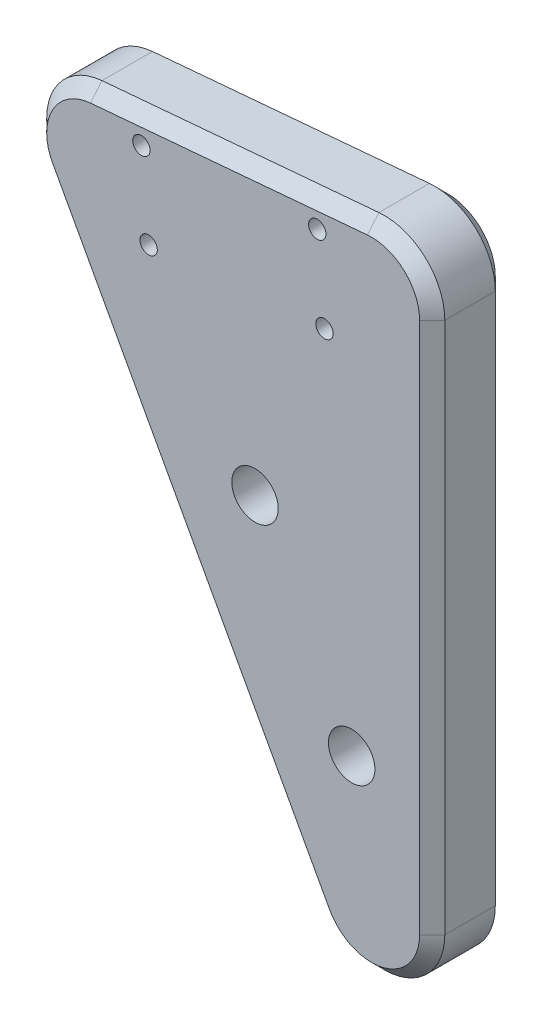
SolidWorks part; units mm, degrees
ref_plane "Front Plane" through (0, 0, 0) normal (0, 0, 1) x (1, 0, 0)
ref_plane "Top Plane" through (0, 0, 0) normal (0, 1, 0) x (1, 0, 0)
ref_plane "Right Plane" through (0, 0, 0) normal (1, 0, 0) x (0, 0, -1)
sketch "Sketch1" plane through (0, 0, 0) normal (0, 0, 1) x (1, 0, 0)
  line L0 (0, 0) -> (54.7145, -100.3535)
  line L1 (54.7145, -100.3535) -> (54.7145, 4.7869)
  line L3 (0, 0) -> (54.7145, 4.7869)
  line L4 (0, 0) -> (100.7995, 0) construction
  line L5 (33.4366, -61.3271) -> (80.8296, -35.4876) construction
  line L6 (19.05, -12.3567) -> (17.5047, 5.3065) construction
  circle A0 centre (44.587, -55.2477) radius 2.921
  circle A1 centre (32.4282, -32.947) radius 2.921
  circle A2 centre (40.2575, -0.0475) radius 1.0922
  circle A3 centre (19.05, -12.3567) radius 1.0922
  circle A4 centre (41.1651, -10.4219) radius 1.0922
  circle A5 centre (18.1424, -1.9823) radius 1.0922
  point P20 (0, 0)
  point P21 (0, 0)
  point P22 (0, 0)
  dimension "D4" = 5.842
  dimension "D8" = 2.1844
  dimension "D1" = 28.6
  dimension "D2" = 5
  dimension "D3" = 114.3
  dimension "D5" = 25.4
  dimension "D6" = 12.7
  dimension "D7" = 12.7
  dimension "D9" = 3.556
  dimension "D10" = 13.97
  dimension "D11" = 22.1996
  dimension "D12" = 19.05
  dimension "D13" = 44.45
  dimension "D14" = 10.414
  dimension "D15" = 22.1996
  dimension "D16" = 22.1996
  dimension "D17" = 3.556
extrude "Boss-Extrude1" add sketch "Sketch1" along normal blind 9.525
fillet "Fillet1" radius 7.62 3 edges at (54.7145, -100.3535, 4.7625) (0, 0, 4.7625) (54.7145, 4.7869, 4.7625)
chamfer "Chamfer1" distance 1.5875 angle 45 12 edges at (5.5489, -2.9753, 0) (22.9892, -42.1652, 0) (48.9766, -77.8429, 0) (54.7145, -36.9939, 0) (29.0153, 2.5385, 0) (52.2425, 2.0892, 0) (48.9766, -77.8429, 9.525) (22.9892, -42.1652, 9.525) (5.5489, -2.9753, 9.525) (29.0153, 2.5385, 9.525) (52.2425, 2.0892, 9.525) (54.7145, -36.9939, 9.525)
